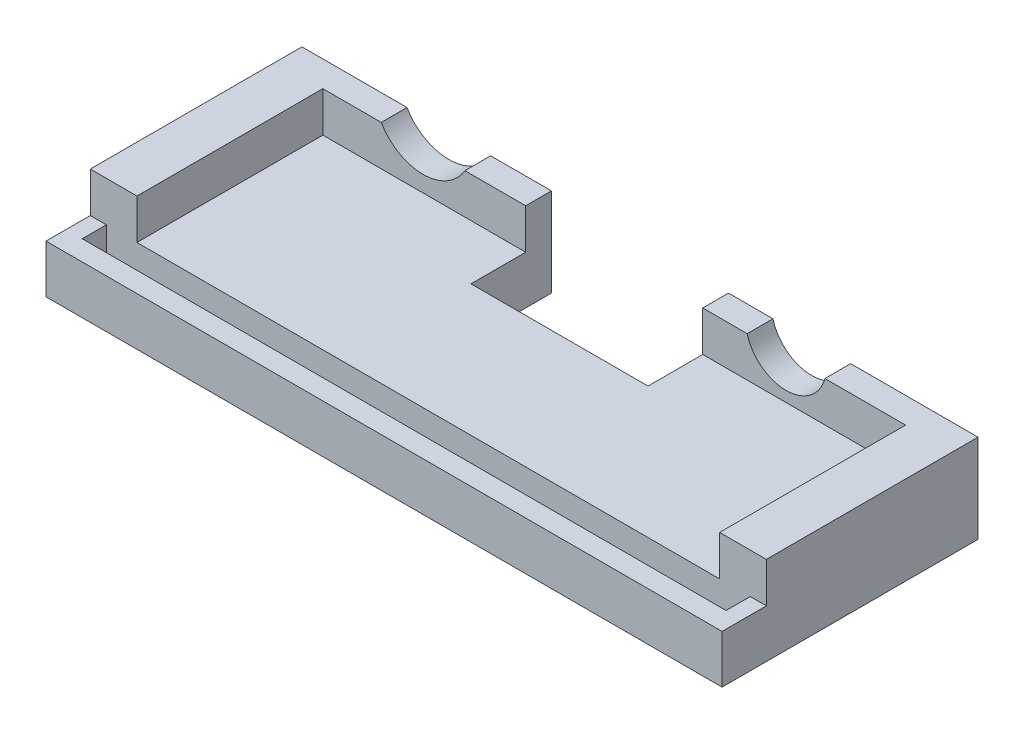
SolidWorks part; units mm, degrees
ref_plane "前视基准面" through (0, 0, 0) normal (0, 0, 1) x (1, 0, 0)
ref_plane "上视基准面" through (0, 0, 0) normal (0, 1, 0) x (1, 0, 0)
ref_plane "右视基准面" through (0, 0, 0) normal (1, 0, 0) x (0, 0, -1)
other "Configuration Table"
sketch "草图1" plane through (0, 0, 0) normal (0, 1, 0) x (1, 0, 0)
  line L1 (0, 0) -> (84, 0)
  line L2 (0, 0) -> (0, -31.8)
  line L3 (0, -31.8) -> (84, -31.8)
  line L4 (84, 0) -> (84, -31.8)
  dimension "D1" = 84
  dimension "D2" = 31.8
extrude "凸台-拉伸1" add sketch "草图1" along normal blind 6 contours L3 L4 L1 L2
sketch "草图2" plane through (0, 6, 0) normal (0, 1, 0) x (1, 0, 0)
  line L0 (0, 0) -> (0, -31.8) construction
  line L1 (2, -29.3) -> (82, -29.3)
  line L2 (2, -29.3) -> (2, -26.3)
  line L3 (2, -26.3) -> (82, -26.3)
  line L4 (82, -29.3) -> (82, -26.3)
  line L5 (84, 0) -> (84, -31.8) construction
  line L6 (0, -31.8) -> (84, -31.8) construction
  dimension "D1" = 2
  dimension "D2" = 2
  dimension "D3" = 2.5
  dimension "D4" = 3
extrude "切除-拉伸1" cut sketch "草图2" against normal blind 3 contours L1 L4 L3 L2
sketch "草图3" plane through (0, 6, 0) normal (0, 1, 0) x (1, 0, 0)
  line L0 (0, 0) -> (0, -31.8) construction
  line L1 (0, 0) -> (84, 0)
  line L2 (0, 0) -> (0, -26.3)
  line L3 (0, -26.3) -> (84, -26.3)
  line L4 (84, 0) -> (84, -26.3)
  line L5 (84, 0) -> (84, -31.8) construction
  line L6 (2, -26.3) -> (82, -26.3) construction
  line L8 (5.8, -3.2) -> (78.2, -3.2)
  line L9 (5.8, -3.2) -> (5.8, -26.3)
  line L10 (5.8, -26.3) -> (78.2, -26.3)
  line L11 (78.2, -3.2) -> (78.2, -26.3)
  line L12 (31, 0) -> (53, 0)
  line L13 (31, 0) -> (31, -10)
  line L14 (31, -10) -> (53, -10)
  line L15 (53, 0) -> (53, -10)
  line M9 (0, 0) -> (0, -31.8)
  line M11 (84, -31.8) -> (84, 0)
  line M12 (84, 0) -> (0, 0)
  line M15 (2, -26.3) -> (82, -26.3)
  dimension "D1" = 5.8
  dimension "D2" = 5.8
  dimension "D3" = 3.2
  dimension "D4" = 26.3
  dimension "D5" = 10
  dimension "D6" = 31
  dimension "D7" = 31
extrude "凸台-拉伸2" add sketch "草图3" along normal blind 5 contours L13 L3 L9 L8 M12 M9 M15 | L15 L8 L11 L3 M12 M15 M11 region at (15.5, 6, 0.4065) region at (68.5, 6, 0.4065)
sketch "草图4" plane through (0, 0, 0) normal (0, 0, -1) x (-1, 0, 0)
  circle A0 centre (-63.35, 12.3) radius 5
  circle A1 centre (-18.25, 14) radius 6
  point P4 (0, 0)
  point P5 (0, 0)
  point P6 (0, 0)
  dimension "D1" = 12
  dimension "D2" = 10
extrude "切除-拉伸2" cut sketch "草图4" against normal through all contours A0 | A1
extrude "切除-拉伸3" cut sketch "草图3<3>" against normal through all contours L15 L1 L13 L8 | L15 L8 L13 L14 region at (42, 6, 1.6) region at (42, 6, 6.6)
sketch "草图3<3>" plane through (0, 6, 0) normal (0, 1, 0) x (1, 0, 0) same geometry as "草图3"
